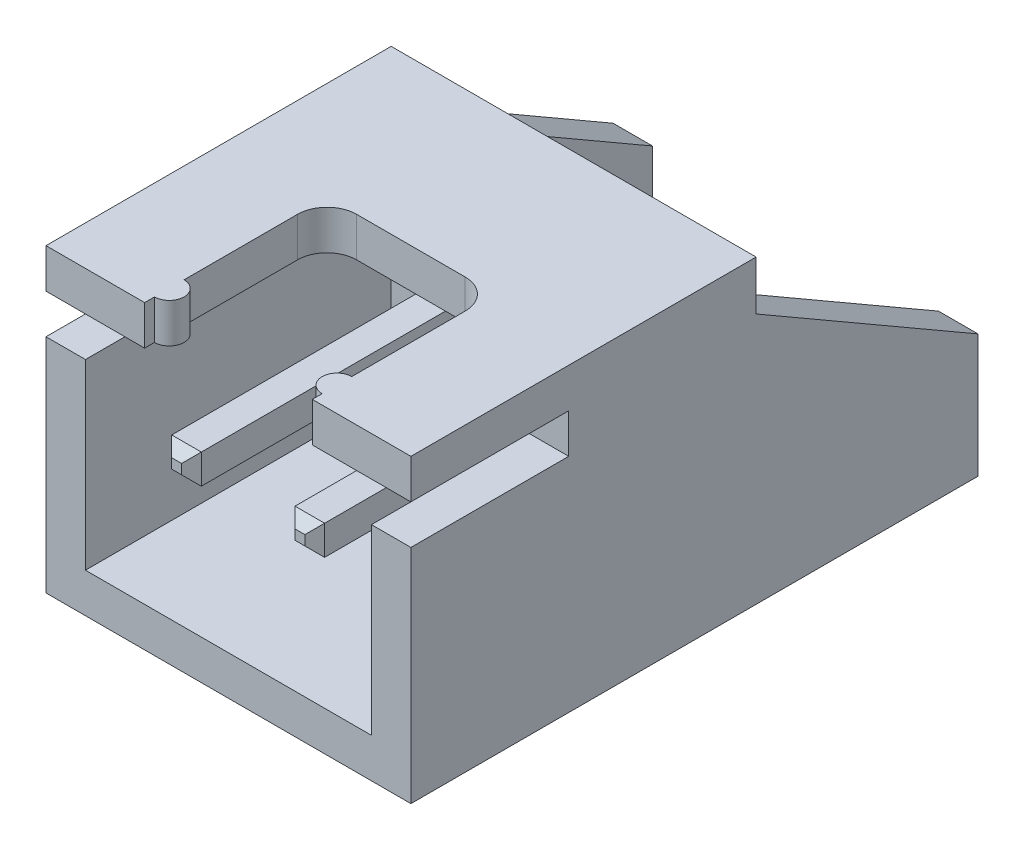
SolidWorks part; units mm, degrees
ref_plane "Plan de face" through (0, 0, 0) normal (0, 0, 1) x (1, 0, 0)
ref_plane "Plan de dessus" through (0, 0, 0) normal (0, 1, 0) x (1, 0, 0)
ref_plane "Plan de droite" through (0, 0, 0) normal (1, 0, 0) x (0, 0, -1)
sketch "Esquisse1" plane through (0, 0, 0) normal (0, 1, 0) x (1, 0, 0)
  line L0 (0.8, 11.5) -> (0.8, 7)
  line L1 (0, 0) -> (7.4, 0)
  line L2 (0, 0) -> (0, 11.5)
  line L3 (0, 11.5) -> (0.8, 11.5)
  line L4 (7.4, 0) -> (7.4, 11.5)
  line L5 (0.8, 7) -> (6.6, 7)
  line L6 (6.6, 7) -> (6.6, 11.5)
  line L7 (6.6, 11.5) -> (7.4, 11.5)
  dimension "largeur boitier" = 7.4
  dimension "D2" = 11.5
  dimension "D3" = 0.8
  dimension "D4" = 0.8
  dimension "D5" = 4.5
extrude "Extrusion1" add sketch "Esquisse1" along normal blind 6.1
shell "Coque1" thickness 0.8 removed face at (3.7, 3.05, 0)
sketch "Esquisse2" plane through (7.4, 0, 0) normal (1, 0, 0) x (0, 0, -1)
  line L1 (11.5, 6.1) -> (7, 6.1) construction
  line L2 (11.5, 6.1) -> (11.5, 0) construction
  line L3 (11.5, 6.1) -> (11.5, 2.5)
  line L4 (11.5, 6.1) -> (7, 6.1)
  line L5 (7, 6.1) -> (7, 5.1)
  line L6 (7, 5.1) -> (11.5, 2.5)
  line L7 (0, 0) -> (11.5, 0) construction
  dimension "D1" = 1
  dimension "D2" = 2.5
extrude "Enlèv. mat.-Extru.1" cut sketch "Esquisse2" against normal through all
sketch "Esquisse3" plane through (0, 5.3, 0) normal (0, 1, 0) x (-1, 0, 0)
  line L0 (-3.7, 0) -> (-3.7, -7) construction
  line L1 (0, 0) -> (-7.4, 0) construction
  line L2 (-7.4, -7) -> (0, -7) construction
  line L3 (-3.95, 0) -> (-5.4, 0)
  line L4 (-3.95, 0) -> (-3.95, -3.7)
  line L5 (-3.95, -3.7) -> (-4.8, -3.7)
  line L6 (-7.4, 0) -> (-7.4, -7) construction
  line L7 (-5.4, -3.1) -> (-5.4, -0.8)
  line L8 (-5.4, -0.2) -> (-5.4, 0)
  line L9 (-2, -0.2) -> (-2, 0)
  line L10 (-2, -3.1) -> (-2, -0.8)
  line L11 (-3.45, -3.7) -> (-2.6, -3.7)
  line L12 (-3.45, 0) -> (-3.45, -3.7)
  line L13 (-3.45, 0) -> (-2, 0)
  line L14 (-6.6, 0) -> (-6.6, -6.2) construction
  line L15 (-6.6, 0) -> (-6.6, -3.2)
  line L16 (-7.4, 0) -> (-7.4, -3.2)
  line L17 (-6.6, 0) -> (-7.4, 0)
  line L18 (-7.4, -3.2) -> (-6.6, -3.2)
  line L19 (0, -3.2) -> (-0.8, -3.2)
  line L20 (-0.8, 0) -> (0, 0)
  line L21 (0, 0) -> (0, -3.2)
  line L22 (-0.8, 0) -> (-0.8, -3.2)
  arc A0 (-5.4, -0.8) -> (-5.4, -0.2) centre (-5.4, -0.5) ccw
  arc A1 (-5.4, -3.1) -> (-4.8, -3.7) centre (-4.8, -3.1) ccw
  arc A2 (-2, -3.1) -> (-2.6, -3.7) centre (-2.6, -3.1) cw
  arc A3 (-2, -0.8) -> (-2, -0.2) centre (-2, -0.5) cw
  dimension "D3" = 0.6
  dimension "D6" = 0.6
  dimension "D1" = 2
  dimension "D2" = 1.45
  dimension "D4" = 0.2
  dimension "D5" = 3.7
  dimension "D7" = 3.2
extrude "Enlèv. mat.-Extru.3" cut sketch "Esquisse3" along normal up to next contours L7 A0 L8 L3 L4 L5 A1 | L12 L11 A2 L10 A3 L9 L13
extrude "Enlèv. mat.-Extru.4" cut sketch "Esquisse3<4>" against normal blind 0.8 contours L18 L15 L17 L16 | L19 L22 L20 L21
sketch "Esquisse3<4>" plane through (0, 5.3, 0) normal (0, 1, 0) x (-1, 0, 0) same geometry as "Esquisse3"
ref_plane "Plan1" through (2.45, 0, 0) normal (1, 0, 0) x (0, 0, -1)
sketch "Esquisse4" plane through (2.45, 0, 0) normal (1, 0, 0) x (0, 0, -1)
  line L0 (9.2, 0) -> (9.2, 3.35)
  line L1 (0.2, 3.35) -> (9.2, 3.35)
  line L2 (0, 4.5) -> (0, 0) construction
  line L3 (0, 0) -> (11.5, 0) construction
  line L4 (11.5, 0) -> (0, 0) construction
  dimension "D1" = 9.2
  dimension "D2" = 3.35
  dimension "D3" = 0.2
extrude "pico01" add sketch "Esquisse4" along normal mid plane 0.6 thin thin type mid plane wall 0.6
chamfer "Chanfrein1" distance 0.2 angle 45 4 edges at (2.15, 3.35, -0.2) (2.45, 3.05, -0.2) (2.75, 3.35, -0.2) (2.45, 3.65, -0.2)
fillet "Congé1" radius 0.6 1 edges at (2.45, 3.05, -8.9)
fillet "Congé2" radius 1.2 1 edges at (2.45, 3.65, -9.5)
sketch "Esquisse5" plane through (0, 0, 0) normal (0, -1, 0) x (1, 0, 0)
  line L0 (2.45, -9.5) -> (2.45, -8.9) construction
  line L1 (2.75, -9.5) -> (2.15, -9.5) construction
  line L2 (2.75, -8.9) -> (2.15, -8.9) construction
  line L4 (2.75, -9.5) -> (2.75, -8.9) construction
  line L5 (2.75, -9.2) -> (2.15, -9.2) construction
  line L6 (2.15, -9.5) -> (2.15, -8.9) construction
  circle A0 centre (2.45, -9.2) radius 0.3
extrude "Extrusion2" add sketch "Esquisse5" along normal blind 2
pattern_linear "Répétition linéaire1" count 2 spacing 2.5 along (1, 0, 0) of "pico01", "Chanfrein1", "Congé1", "Congé2", "Extrusion2"
ref_plane "Plan2" through (2.45, 0, 0) normal (1, 0, 0) x (0, 0, -1)
ref_plane "Plan3" through (0, 0, -9.2) normal (0, 0, 1) x (1, 0, 0)
sketch "Esquisse6" plane through (0, 6.1, 0) normal (0, 1, 0) x (-1, 0, 0)
  line L1 (-3.45, 0) -> (-3.95, 0)
  line L2 (-3.45, 0) -> (-3.45, -3.7)
  line L3 (-3.45, -3.7) -> (-3.95, -3.7)
  line L4 (-3.95, 0) -> (-3.95, -3.7)
extrude "Enlèv. mat.-Extru.5" cut sketch "Esquisse6" against normal up to next
equation "\"largeur boitier@Esquisse1\" = (\"D1@Répétition linéaire1\"-1)*2.5+4.9"
